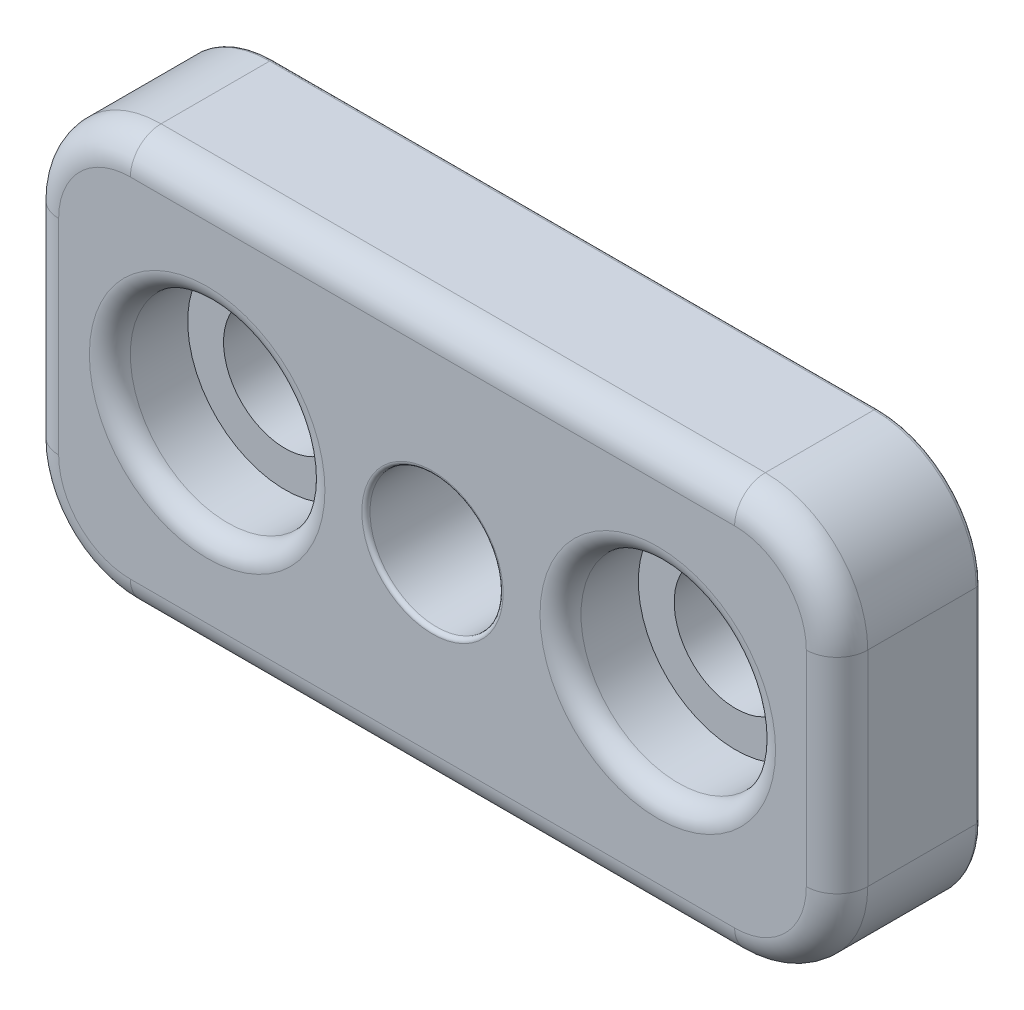
SolidWorks part; units mm, degrees
ref_plane "Front Plane" through (0, 0, 0) normal (0, 0, 1) x (1, 0, 0)
ref_plane "Top Plane" through (0, 0, 0) normal (0, 1, 0) x (1, 0, 0)
ref_plane "Right Plane" through (0, 0, 0) normal (1, 0, 0) x (0, 0, -1)
sketch "Sketch1" plane through (0, 0, 0) normal (0, 0, 1) x (1, 0, 0)
  line L0 (0, 5.5269) -> (0, -6.8276) construction
  line L1 (19.75, -10) -> (-19.75, -10)
  line L2 (19.75, -10) -> (19.75, 10)
  line L3 (19.75, 10) -> (-19.75, 10)
  line L4 (-19.75, -10) -> (-19.75, 10)
  line L5 (19.75, -10) -> (-19.75, 10) construction
  line L6 (19.75, 10) -> (-19.75, -10) construction
  circle A0 centre (0, 0) radius 3.25
  circle A1 centre (-11, 0) radius 3
  circle A2 centre (-11, 0) radius 4.75
  circle A3 centre (11, 0) radius 4.75
  circle A4 centre (11, 0) radius 3
  point P0 (0, 0)
  dimension "D2" = 6.5
  dimension "D3" = 6
  dimension "D4" = 9.5
  dimension "D5" = 4
  dimension "D6" = 3
  dimension "D1" = 20
extrude "Boss-Extrude1" add sketch "Sketch1" along normal mid plane 7 contours L4 L1 L2 L3 A0 A2 A3 | A2 A1 | A3 A4 region at (0, -9.5573, 0) region at (-15.6156, 0, 0) region at (6.3844, 0, 0)
extrude "Cut-Extrude1" cut sketch "Sketch1<3>" against normal offset from surface (3.8 mm away) 3.2 from surface contours A2 A1 | A3 A4 region at (-15.6156, 0, 0) region at (6.3844, 0, 0) up to face at (0, 0, -3.5) starting at face at (0, 0, 3.5)
sketch "Sketch1<3>" plane through (0, 0, 0) normal (0, 0, 1) x (1, 0, 0) same geometry as "Sketch1"
fillet "Fillet1" radius 5 4 edges at (19.75, 10, 0) (19.75, -10, 0) (-19.75, -10, 0) (-19.75, 10, 0)
fillet "Fillet2" radius 1.5 8 edges at (18.2855, 8.5355, 3.5) (19.75, 0, 3.5) (18.2855, -8.5355, 3.5) (0, -10, 3.5) (-18.2855, -8.5355, 3.5) (-19.75, 0, 3.5) (-18.2855, 8.5355, 3.5) (0, 10, 3.5)
fillet "Fillet3" radius 1 2 edges at (15.75, 0, 3.5) (-6.25, 0, 3.5)
fillet "Fillet4" radius 0.2 12 edges at (-8, 0, -3.5) (14, 0, -3.5) (3.25, 0, -3.5) (-18.2855, 8.5355, -3.5) (-19.75, 0, -3.5) (-18.2855, -8.5355, -3.5) (0, -10, -3.5) (18.2855, -8.5355, -3.5) (19.75, 0, -3.5) (18.2855, 8.5355, -3.5) (0, 10, -3.5) (3.25, 0, 3.5)
